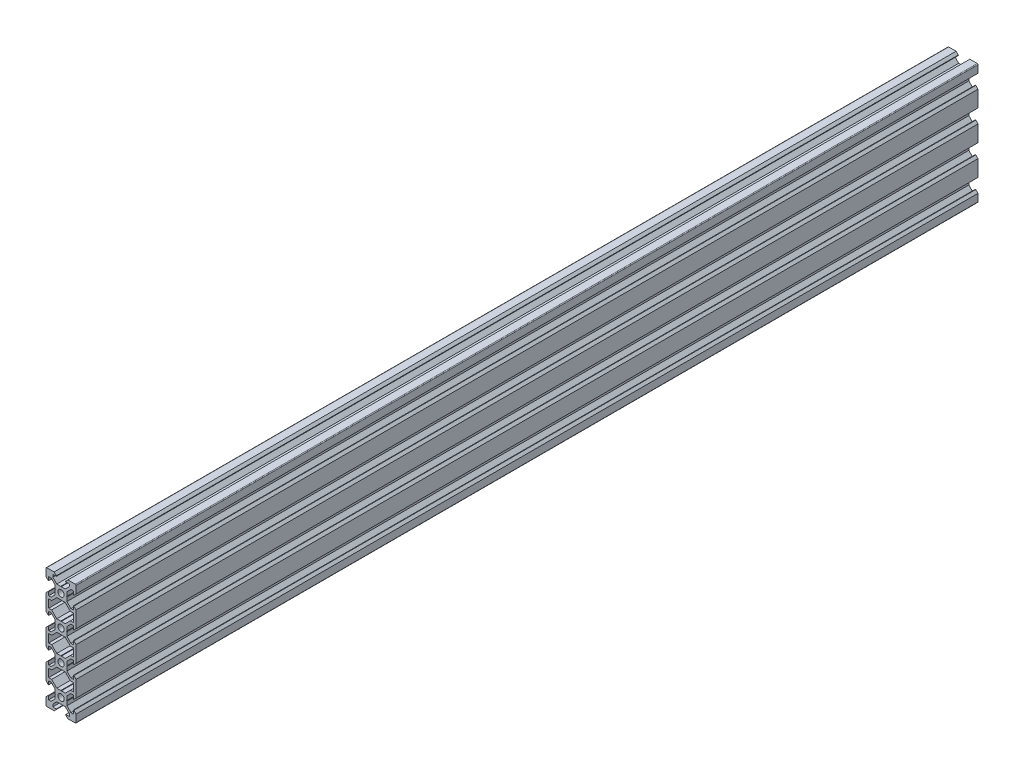
SolidWorks part; units mm, degrees
ref_plane "Plan de face" through (0, 0, 0) normal (0, 0, 1) x (1, 0, 0)
ref_plane "Plan de dessus" through (0, 0, 0) normal (0, 1, 0) x (1, 0, 0)
ref_plane "Plan de droite" through (0, 0, 0) normal (1, 0, 0) x (0, 0, -1)
ref_axis "Axe" through (0, 0, -13.782) along (0, 0, 1)
sketch "Esquisse1" plane through (0, 0, 0) normal (0, 0, 1) x (1, 0, 0)
  line L0 (0, 27.6392) -> (0, -27.6392) construction
  line L1 (-33.6074, 0) -> (33.6074, 0) construction
  line L2 (0, 0) -> (-22.2114, 22.2114) construction
  line L3 (-9.5, 10) -> (-4.58, 10)
  line L4 (-4.58, 10) -> (-3.125, 8.545)
  line L5 (-3.125, 8.545) -> (-3.125, 8.2)
  line L6 (-3.125, 8.2) -> (-5.5, 8.2)
  line L7 (-2.8393, 3.9) -> (-5.5, 6.5607)
  line L8 (-2.8393, 3.9) -> (-0.21, 3.9)
  line L9 (-5.5, 6.5607) -> (-5.5, 8.2)
  line L10 (0, 3.69) -> (0, 2.1)
  line L11 (-3.9, 2.8393) -> (-6.5607, 5.5)
  line L12 (-8.545, 3.125) -> (-8.2, 3.125)
  line L13 (-8.2, 3.125) -> (-8.2, 5.5)
  line L14 (-6.5607, 5.5) -> (-8.2, 5.5)
  line L15 (-10, 4.58) -> (-8.545, 3.125)
  line L16 (-10, 9.5) -> (-10, 4.58)
  line L17 (-0.21, 3.9) -> (0, 3.69)
  line L18 (-3.9, 2.8393) -> (-3.9, 0.21)
  line L19 (-6.2393, -12.7) -> (-8.2, -12.7)
  line L20 (-3.9, 0.21) -> (-3.69, 0)
  line L21 (-0.21, -3.9) -> (0, -3.69)
  line L22 (0, -3.69) -> (0, -2.1)
  line L23 (-6.5607, -5.5) -> (-8.2, -5.5)
  line L24 (-2.8393, -3.9) -> (-0.21, -3.9)
  line L25 (-8.545, -3.125) -> (-8.2, -3.125)
  line L26 (-10, -4.58) -> (-8.545, -3.125)
  line L27 (-8.2, -3.125) -> (-8.2, -5.5)
  line L28 (-2.8393, -3.9) -> (-6.2393, -7.3)
  line L29 (-3.9, -2.8393) -> (-6.5607, -5.5)
  line L30 (-3.9, -2.8393) -> (-3.9, -0.21)
  line L31 (-3.9, -0.21) -> (-3.69, 0)
  line L32 (-6.2393, -7.3) -> (-8.2, -7.3)
  line L33 (-8.2, -7.3) -> (-8.2, -12.7)
  line L34 (-8.2, -10) -> (-10, -10) construction
  line L35 (-10, -15.42) -> (-10, -4.58)
  line L36 (-3.9, -19.79) -> (-3.69, -20)
  line L37 (-3.9, -17.1607) -> (-3.9, -19.79)
  line L38 (-3.9, -17.1607) -> (-6.5607, -14.5)
  line L39 (-2.8393, -16.1) -> (-6.2393, -12.7)
  line L40 (-8.2, -16.875) -> (-8.2, -14.5)
  line L41 (-10, -15.42) -> (-8.545, -16.875)
  line L42 (-8.545, -16.875) -> (-8.2, -16.875)
  line L43 (-2.8393, -16.1) -> (-0.21, -16.1)
  line L44 (-6.5607, -14.5) -> (-8.2, -14.5)
  line L45 (0, -16.31) -> (0, -17.9)
  line L46 (-0.21, -16.1) -> (0, -16.31)
  line L47 (-8.2, -30) -> (-10, -30) construction
  line L48 (-3.69, -20) -> (0, -20) construction
  line L49 (-0.21, -23.9) -> (0, -23.69)
  line L50 (0, -23.69) -> (0, -22.1)
  line L51 (-6.5607, -25.5) -> (-8.2, -25.5)
  line L52 (-2.8393, -23.9) -> (-0.21, -23.9)
  line L53 (-8.545, -23.125) -> (-8.2, -23.125)
  line L54 (-10, -24.58) -> (-8.545, -23.125)
  line L55 (-8.2, -23.125) -> (-8.2, -25.5)
  line L56 (-2.8393, -23.9) -> (-6.2393, -27.3)
  line L57 (-3.9, -22.8393) -> (-6.5607, -25.5)
  line L58 (-3.9, -22.8393) -> (-3.9, -20.21)
  line L59 (-3.9, -20.21) -> (-3.69, -20)
  line L60 (-10, -24.58) -> (-10, -35.42)
  line L61 (-8.2, -32.7) -> (-8.2, -27.3)
  line L62 (-3.69, -40) -> (0, -40) construction
  line L63 (-8.2, -50) -> (-10, -50) construction
  line L64 (0, -60) -> (-22.2114, -82.2114) construction
  line L65 (-33.6074, -60) -> (33.6074, -60) construction
  line L66 (0, -87.6392) -> (0, -32.3608) construction
  line L67 (-6.2393, -32.7) -> (-8.2, -32.7)
  line L68 (-3.9, -39.79) -> (-3.69, -40)
  line L69 (-3.9, -37.1607) -> (-3.9, -39.79)
  line L70 (-3.9, -37.1607) -> (-6.5607, -34.5)
  line L71 (-2.8393, -36.1) -> (-6.2393, -32.7)
  line L72 (-8.2, -36.875) -> (-8.2, -34.5)
  line L73 (-10, -35.42) -> (-8.545, -36.875)
  line L74 (-8.545, -36.875) -> (-8.2, -36.875)
  line L75 (-6.2393, -27.3) -> (-8.2, -27.3)
  line L76 (-2.8393, -36.1) -> (-0.21, -36.1)
  line L77 (-6.5607, -34.5) -> (-8.2, -34.5)
  line L78 (0, -36.31) -> (0, -37.9)
  line L79 (-0.21, -36.1) -> (0, -36.31)
  line L80 (-0.21, -43.9) -> (0, -43.69)
  line L81 (0, -43.69) -> (0, -42.1)
  line L82 (-6.5607, -45.5) -> (-8.2, -45.5)
  line L83 (-2.8393, -43.9) -> (-0.21, -43.9)
  line L84 (-8.545, -43.125) -> (-8.2, -43.125)
  line L85 (-10, -44.58) -> (-8.545, -43.125)
  line L86 (-8.2, -43.125) -> (-8.2, -45.5)
  line L87 (-2.8393, -43.9) -> (-6.2393, -47.3)
  line L88 (-3.9, -42.8393) -> (-6.5607, -45.5)
  line L89 (-3.9, -42.8393) -> (-3.9, -40.21)
  line L90 (-3.9, -40.21) -> (-3.69, -40)
  line L91 (-10, -44.58) -> (-10, -55.42)
  line L92 (-8.2, -52.7) -> (-8.2, -47.3)
  line L93 (-6.2393, -52.7) -> (-8.2, -52.7)
  line L94 (-3.9, -59.79) -> (-3.69, -60)
  line L95 (-3.9, -57.1607) -> (-3.9, -59.79)
  line L96 (-3.9, -57.1607) -> (-6.5607, -54.5)
  line L97 (-2.8393, -56.1) -> (-6.2393, -52.7)
  line L98 (-8.2, -56.875) -> (-8.2, -54.5)
  line L99 (-10, -55.42) -> (-8.545, -56.875)
  line L100 (-8.545, -56.875) -> (-8.2, -56.875)
  line L101 (-2.8393, -56.1) -> (-0.21, -56.1)
  line L102 (-6.5607, -54.5) -> (-8.2, -54.5)
  line L103 (0, -56.31) -> (0, -57.9)
  line L104 (-0.21, -56.1) -> (0, -56.31)
  line L105 (-3.9, -60.21) -> (-3.69, -60)
  line L106 (-6.2393, -47.3) -> (-8.2, -47.3)
  line L107 (-3.9, -62.8393) -> (-3.9, -60.21)
  line L108 (-0.21, -63.9) -> (0, -63.69)
  line L109 (-10, -69.5) -> (-10, -64.58)
  line L110 (-10, -64.58) -> (-8.545, -63.125)
  line L111 (-6.5607, -65.5) -> (-8.2, -65.5)
  line L112 (-8.2, -63.125) -> (-8.2, -65.5)
  line L113 (-8.545, -63.125) -> (-8.2, -63.125)
  line L114 (-3.9, -62.8393) -> (-6.5607, -65.5)
  line L115 (0, -63.69) -> (0, -62.1)
  line L116 (-5.5, -66.5607) -> (-5.5, -68.2)
  line L117 (-2.8393, -63.9) -> (-0.21, -63.9)
  line L118 (-2.8393, -63.9) -> (-5.5, -66.5607)
  line L119 (-3.125, -68.2) -> (-5.5, -68.2)
  line L120 (-3.125, -68.545) -> (-3.125, -68.2)
  line L121 (-4.58, -70) -> (-3.125, -68.545)
  line L122 (-9.5, -70) -> (-4.58, -70)
  arc A0 (0, -2.1) -> (0, 2.1) centre (0, 0) cw
  arc A1 (-9.5, 10) -> (-10, 9.5) centre (-9.5, 9.5) ccw
  arc A2 (0, -42.1) -> (0, -37.9) centre (0, -40) cw
  arc A3 (-9.5, -70) -> (-10, -69.5) centre (-9.5, -69.5) cw
  arc A4 (0, -17.9) -> (0, -22.1) centre (0, -20) ccw
  arc A5 (0, -57.9) -> (0, -62.1) centre (0, -60) ccw
  point P4 (0, 0)
  point P7 (0, 0)
  point P30 (-10, 10)
  point P60 (0, -20)
  point P146 (-10, -70)
  dimension "D5" = 11
  dimension "D2" = 2.1
  dimension "D3" = 6.25
  dimension "D10" = 0.5
  dimension "D4" = 9.16
  dimension "D6" = 1.5
  dimension "D7" = 1.8
  dimension "D8" = 4.3
  dimension "D9" = 20
  dimension "D11" = 0.42
  dimension "D12" = 10
  dimension "D13" = 1.8
extrude "Boss.-Extru.1" add sketch "Esquisse1" along normal blind 600
sketch "Esquisse3" plane through (0, 0, 600) normal (0, 0, 1) x (1, 0, 0)
  line L0 (0, 0) -> (-9.8536, 9.8536) construction
  line L1 (-8.2, 8.2) -> (-8.2, 6.57)
  line L2 (-8.2, 6.57) -> (-7.54, 6.57)
  line L3 (-7.54, 6.57) -> (-6.57, 7.54)
  line L4 (-8.2, 3.125) -> (-8.2, 5.5) construction
  line L5 (-6.57, 8.2) -> (-6.57, 7.54)
  line L6 (-8.2, 8.2) -> (-6.57, 8.2)
  line L7 (-5.5, 6.5607) -> (-5.5, 8.2) construction
  line L8 (-10, -30) -> (6.918, -30) construction
  line L9 (-10, -24.58) -> (-10, -35.42) construction
  line L10 (-8.2, -68.2) -> (-6.57, -68.2)
  line L11 (-6.57, -68.2) -> (-6.57, -67.54)
  line L12 (-7.54, -66.57) -> (-6.57, -67.54)
  line L13 (-8.2, -66.57) -> (-7.54, -66.57)
  line L14 (-8.2, -68.2) -> (-8.2, -66.57)
  arc A0 (-9.5, 10) -> (-10, 9.5) centre (-9.5, 9.5) ccw construction
  point P13 (-7.055, 7.055)
  point P14 (-6.57, 7.87)
  point P26 (-7.055, -67.055)
  dimension "D1" = 1.07
extrude "Enlèv. mat.-Extru.1" [suppressed] cut sketch "Esquisse3" against normal through all
mirror "Symétrie1" of "Enlèv. mat.-Extru.1", "Boss.-Extru.1"
